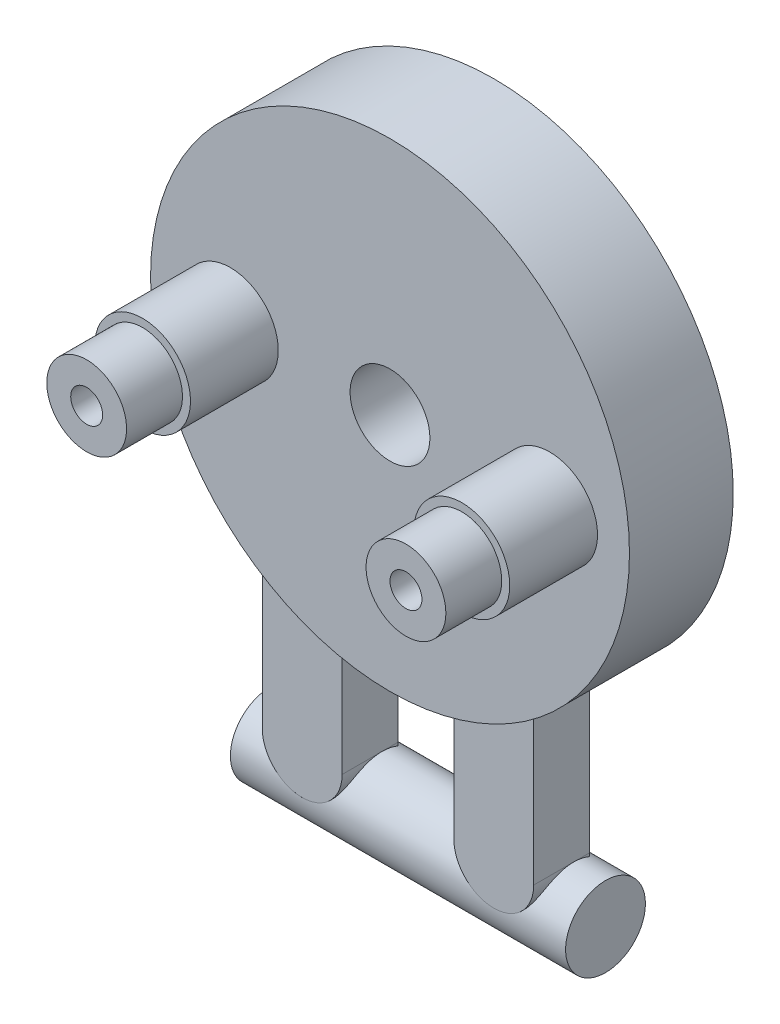
SolidWorks part; units mm, degrees
ref_plane "Front Plane" through (0, 0, 0) normal (0, 0, 1) x (1, 0, 0)
ref_plane "Top Plane" through (0, 0, 0) normal (0, 1, 0) x (1, 0, 0)
ref_plane "Right Plane" through (0, 0, 0) normal (1, 0, 0) x (0, 0, -1)
sketch "Sketch1" plane through (0, 0, 0) normal (0, 0, 1) x (1, 0, 0)
  circle A0 centre (0, 0) radius 15
  dimension "D1" = 30
extrude "Boss-Extrude1" add sketch "Sketch1" along normal mid plane 6.5
sketch "Sketch2" plane through (0, 0, 3.25) normal (0, 0, 1) x (1, 0, 0)
  line L0 (0, 0) -> (0, -24.4763) construction
  line L3 (-8.5, -12.3592) -> (-8.5, -24)
  line L4 (-8.5, -24) -> (-3.5, -24)
  line L5 (-3.5, -14.586) -> (-3.5, -24)
  circle A0 centre (0, 0) radius 15 construction
  arc A1 (-8.5, -12.3592) -> (-3.5, -14.586) centre (0, 0) ccw
  point P10 (-3.5, -8.6358)
  dimension "D1" = 24
  dimension "D2" = 5
  dimension "D3" = 17
extrude "Boss-Extrude2" add sketch "Sketch2" against normal blind 3.5 from offset 0.5 offset against normal yes
fillet "Fillet1" 2 edges at (-3.5, -24, 1) (-8.5, -24, 1) type full round first side face at (-3.5, -19.293, 1) second side face at (-8.5, -18.1796, 1) middle face at (-6, -24, 1)
mirror "Mirror1" about plane through (0, 0, 0) normal (1, 0, 0) of "Fillet1", "Boss-Extrude2"
sketch "Sketch3" plane through (0, 0, 0) normal (1, 0, 0) x (0, 0, -1)
  line L3 (-2.75, -21.5) -> (-2.75, -24) construction
  line L4 (-2.75, -21.5) -> (-2.75, -24) construction
  circle A0 centre (-0.25, -24) radius 2.5
  point P2 (1.6253, -24)
  point P3 (0, 0)
  point P4 (0, 0)
  point P5 (5.1543, -21.5)
  point P7 (-3.3691, -24)
  point P9 (-0.2791, -22.4453)
  point P10 (-0.2242, -18.9602)
  point P11 (1.9986, -24)
  point P14 (0, 0)
  dimension "D1" = 5
extrude "Boss-Extrude3" add sketch "Sketch3" along normal mid plane 21
sketch "Sketch4" plane through (0, 0, 3.25) normal (0, 0, 1) x (1, 0, 0)
  line L0 (0, 0) -> (0, 7.9401) construction
  circle A0 centre (10, 0) radius 3
  point P5 (0, 0)
  point P6 (9.8446, 0)
  dimension "D1" = 6
  dimension "D2" = 20
extrude "Boss-Extrude4" add sketch "Sketch4" along normal blind 5.5
sketch "Sketch5" plane through (0, 0, 8.75) normal (0, 0, 1) x (1, 0, 0)
  line L0 (0, 0) -> (0, 8.4324) construction
  circle A0 centre (10, 0) radius 2.5
  dimension "D1" = 5
extrude "Boss-Extrude5" add sketch "Sketch5" along normal blind 3.5
sketch "Sketch6" plane through (0, 0, 12.25) normal (0, 0, 1) x (1, 0, 0)
  circle A0 centre (10, 0) radius 1
  dimension "D1" = 2
extrude "Cut-Extrude1" cut sketch "Sketch6" against normal up to surface (9 mm away) up to face at (13, 0, 3.25)
mirror "Mirror2" about plane through (0, 0, 0) normal (1, 0, 0) of "Cut-Extrude1", "Boss-Extrude4", "Boss-Extrude5"
sketch "Sketch7" plane through (0, 0, 3.25) normal (0, 0, 1) x (1, 0, 0)
  circle A0 centre (0, 0) radius 2.5
  dimension "D1" = 5
extrude "Cut-Extrude2" cut sketch "Sketch7" against normal through all
